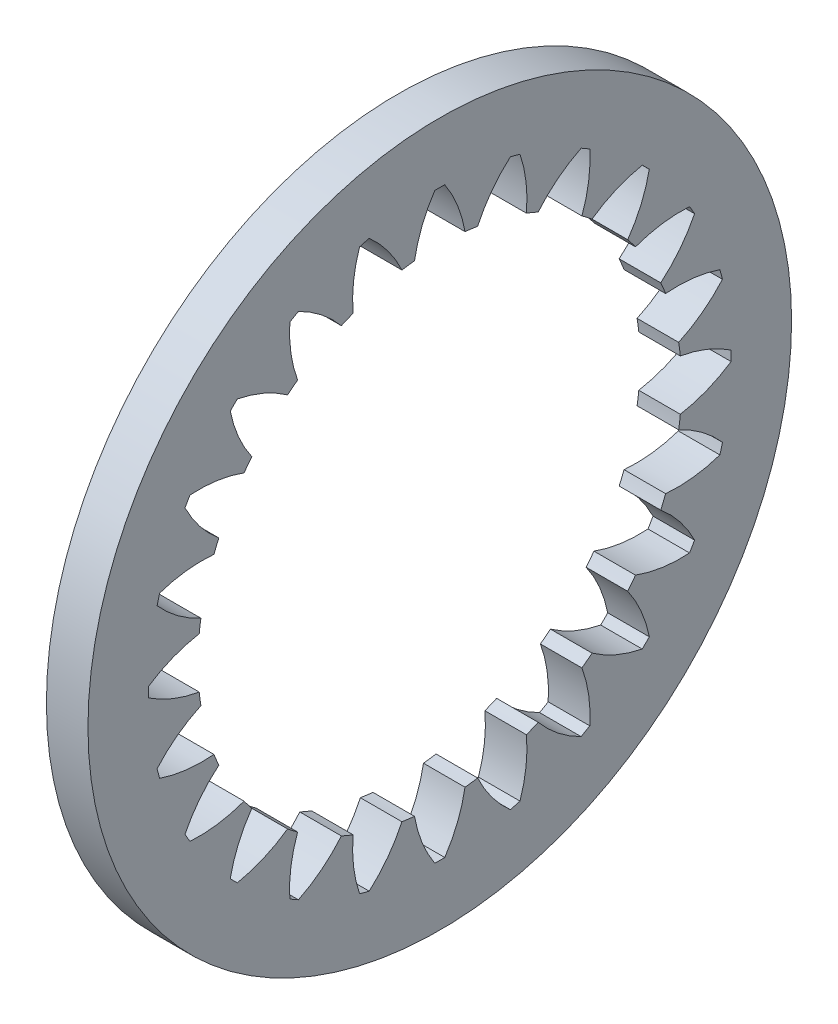
SolidWorks part; units mm, degrees
ref_plane "Plane1" through (0, 0, 0) normal (0, 0, 1) x (1, 0, 0)
ref_plane "Plane2" through (0, 0, 0) normal (0, 1, 0) x (1, 0, 0)
ref_plane "Plane3" through (0, 0, 0) normal (1, 0, 0) x (0, 0, -1)
sketch "HoldingSke" plane through (0, 0, 0) normal (0, 1, 0) x (1, 0, 0)
  line L0 (0, 0) -> (-0.0273, -0.1551)
  line L1 (-15, 0) -> (100, 0) construction
  line L2 (0, 0) -> (-2.1039, 2.3779)
  line L3 (0, 0) -> (-11.863, 4.5341)
  line L4 (0, 0) -> (7.8894, 3.5126)
  line L5 (0, 0) -> (-23.7986, -8.8762)
  line L6 (0, 0) -> (-10.5278, -7.1032)
  line L7 (-2.1039, 2.3779) -> (3.3635, 27.1825)
  line L8 (-76.2, 8.7279) -> (-54.61, 8.7279)
  line L9 (-67.7845, 28.3722) -> (-49.3413, 33.142)
  line L10 (-76.2, 71.12) -> (104.1128, 71.12)
  line L11 (0, 0) -> (-12, 0)
  line L12 (-76.2, 101.6) -> (-75.9714, 101.6)
  line L13 (24.9733, 27.94) -> (52.9518, 28.4284)
  line L14 (24.9733, 27.94) -> (24.9746, 27.94)
  line L15 (24.9733, 27.94) -> (100.4006, 29.5858)
  circle A0 centre (0, 0) radius 101.6
  circle A1 centre (0, 0) radius 12.7
  circle A2 centre (0, 0) radius 12.7
  dimension "Num_teeth" = 24
  dimension "Pitch_radius" = 180.3128
  dimension "Width" = 12
  dimension "Diameter" = 203.2
sketch "BasProSke" plane through (0, 0, 0) normal (0, 1, 0) x (1, 0, 0)
  line L0 (-10, 0) -> (60, 0) construction
  line L1 (0, 69.85) -> (0, 101.6)
  line L2 (0, 69.85) -> (12, 69.85)
  line L3 (12, 69.85) -> (12, 101.6)
  line L4 (12, 101.6) -> (0, 101.6)
  dimension "Thickness" = 12
  dimension "Diameter" = 203.2
revolve "Base-Revolve" add sketch "BasProSke" angle 360 about L0
sketch "TooCutSke" plane through (0, 0, 0) normal (1, 0, 0) x (0, 0, -1)
  line L3 (5.5552, 75.9972) -> (5.5552, 53.6633) construction
  line L4 (0, 0) -> (0, 59.563) construction
  line L5 (0, 0) -> (-8.9185, 67.7429) construction
  line L6 (-30.2541, 62.9855) -> (28.8527, 70.767) construction
  circle A0 centre (0, 0) radius 76.2 construction
  circle A1 centre (0, 0) radius 84.1388 construction
  circle A2 centre (0, 0) radius 66.3956 construction
  circle A3 centre (0, 0) radius 69.8246 construction
  arc A4 (7.2948, 69.4425) -> (1.4425, 84.1264) centre (-30.2541, 62.9855) ccw
  arc A5 (7.2948, 69.4425) -> (-7.2948, 69.4425) centre (0, 0) ccw
  arc A6 (1.4425, 84.1264) -> (-1.4425, 84.1264) centre (0, 0) ccw
  arc A7 (-1.4425, 84.1264) -> (-7.2948, 69.4425) centre (30.2541, 62.9855) ccw
extrude "ToothCut" cut sketch "TooCutSke" along normal through all
fillet "Breaks" [suppressed] radius 0.635
fillet "RootFillets" [suppressed] radius 1.5888
pattern_circular "TeethCuts" count 24 every 15 about axis through (-10, 0, 0) along (1, 0, 0) of "RootFillets", "Breaks", "ToothCut"
equation "' \"Module@HoldingSke\" = 6.35"
equation "' \"Num_teeth@HoldingSke\" = 24"
equation "' \"Ap@HoldingSke\" =  14.5"
equation "' \"Ap@HoldingSke\" = 14.5"
equation "' \"Width@HoldingSke\" = 12"
equation "' \"Diameter@HoldingSke\" = 8 * 25.4"
equation "' \"Show_teeth@HoldingSke\" = 100"
equation "' \"Backlash@HoldingSke\" = 0.009 * 25.4"
equation "' \"Addendum_fac@HoldingSke\" = 1.0"
equation "' \"Dedendum_fac@HoldingSke\" = 1.25"
equation "' \"Dedendum_add@HoldingSke\" = 0.00005 * 25.4"
equation "' \"Clearance_fac@HoldingSke\" = 0.25"
equation "\"Pitch@HoldingSke\" = 1 / \"Module@HoldingSke\" "
equation "\"Overcut_dia@TooCutSke\" = (\"Num_teeth@HoldingSke\" - 2 * \"Addendum_fac@HoldingSke\") / \"Pitch@HoldingSke\" - 0.002 * 25.4"
equation "\"Pitch_dia@TooCutSke\" = \"Num_teeth@HoldingSke\" / \"Pitch@HoldingSke\""
equation "\"Base_dia@TooCutSke\" = \"Num_teeth@HoldingSke\" / \"Pitch@HoldingSke\" * cos((\"Ap@HoldingSke\"  * 3.14159265 / 180)) * 0.90"
equation "\"Root_dia@TooCutSke\" = \"Num_teeth@HoldingSke\"  / \"Pitch@HoldingSke\" + 2 *  \"Dedendum_fac@HoldingSke\"/ \"Pitch@HoldingSke\" + \"Dedendum_add@HoldingSke\" * 2"
equation "\"Half_ang@TooCutSke\" = 180 / \"Num_teeth@HoldingSke\""
equation "\"Half_CT@TooCutSke\" = \"Num_teeth@HoldingSke\" / \"Pitch@HoldingSke\" * sin((3.14159265 / 2 / \"Num_teeth@HoldingSke\")) / 2 + 10 * \"Backlash@HoldingSke\" / 4"
equation "\"Flank_rad@TooCutSke\" = \"Num_teeth@HoldingSke\" / \"Pitch@HoldingSke\" / 4"
equation "\"Radius@RootFillets\"= \"Clearance_fac@HoldingSke\" / \"Pitch@HoldingSke\" + \"Dedendum_add@HoldingSke\""
equation "\"Break_rad@Breaks\" = 0.02 / \"Pitch@HoldingSke\" * 5"
equation "\"Num_teeth@TeethCuts\" = int( \"Show_teeth@HoldingSke\" ) + 1"
equation "\"Num_teeth@TeethCuts\" = ((sgn( \"Num_teeth@TeethCuts\" - \"Num_teeth@HoldingSke\" )-1)*( \"Num_teeth@TeethCuts\" - \"Num_teeth@HoldingSke\" ))/-2+ \"Num_teeth@HoldingSke\""
equation "\"Num_teeth@TeethCuts\" = ((sgn( \"Num_teeth@TeethCuts\" - 2.0)+1)*( \"Num_teeth@TeethCuts\" - 2.0))/2 +2.0"
equation "\"Angle@TeethCuts\" = 360.0 / \"Num_teeth@HoldingSke\""
equation "\"Diameter@BasProSke\" = \"Num_teeth@HoldingSke\"  / \"Pitch@HoldingSke\" + 2 *  \"Dedendum_fac@HoldingSke\"/ \"Pitch@HoldingSke\" + \"Dedendum_add@HoldingSke\" * 2 + 0.002 * 25.4"
equation "\"Diameter@BasProSke\" = ((sgn( \"Diameter@BasProSke\"  - \"Diameter@HoldingSke\" )+1)*( \"Diameter@BasProSke\"  - \"Diameter@HoldingSke\" ))/2 + \"Diameter@HoldingSke\""
equation "\"Inside_diameter@BasProSke\" =  (\"Num_teeth@HoldingSke\" - 2 * \"Addendum_fac@HoldingSke\") / \"Pitch@HoldingSke\" "
equation "\"Thickness@BasProSke\"  = \"Width@HoldingSke\""
